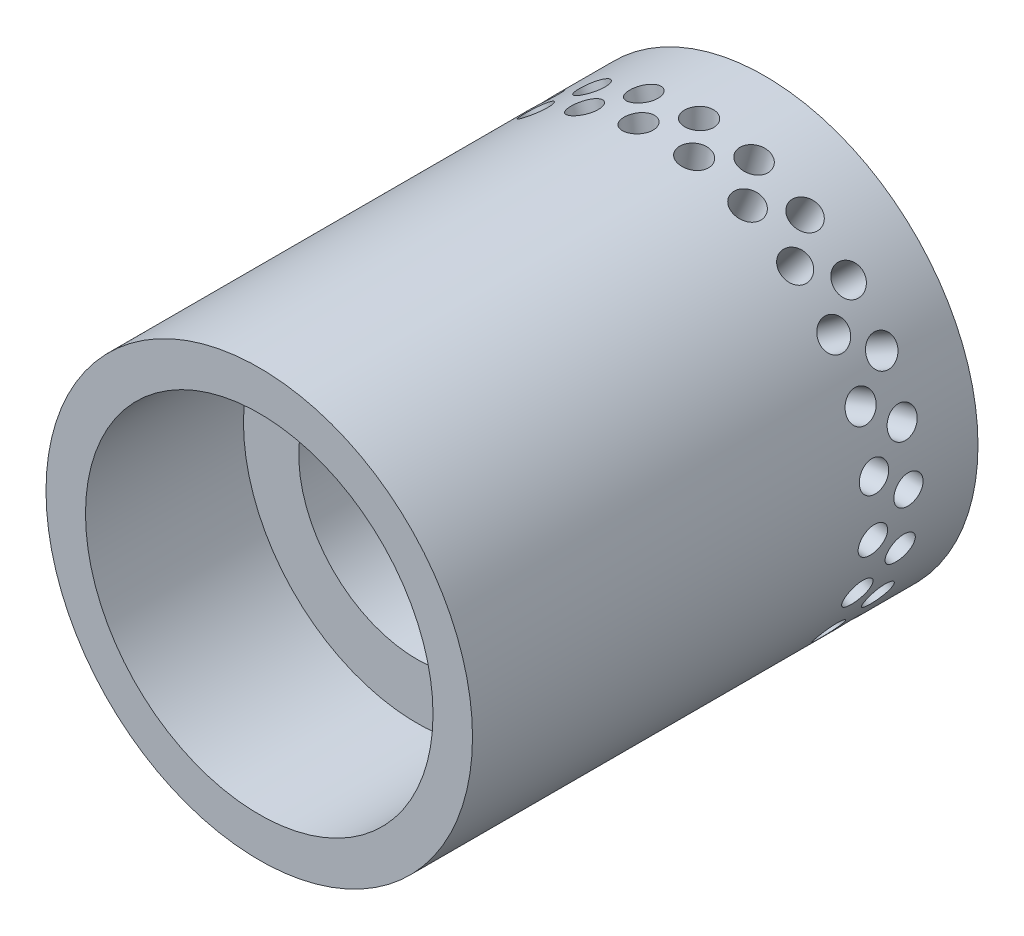
SolidWorks part; units mm, degrees
ref_plane "Front Plane" through (0, 0, 0) normal (0, 0, 1) x (1, 0, 0)
ref_plane "Top Plane" through (0, 0, 0) normal (0, 1, 0) x (1, 0, 0)
ref_plane "Right Plane" through (0, 0, 0) normal (1, 0, 0) x (0, 0, -1)
sketch "Sketch2" plane through (0, 0, 0) normal (0, 0, 1) x (1, 0, 0)
  circle A0 centre (0, 0) radius 13.5
  dimension "D1" = 27
extrude "Boss-Extrude1" add sketch "Sketch2" against normal blind 32
ref_plane "Plane1" through (0, 0, 0) normal (0, 0, 1) x (1, 0, 0)
sketch "Sketch4" plane through (0, 0, 0) normal (0, 0, 1) x (1, 0, 0)
  circle A0 centre (0, 0) radius 11
  dimension "D1" = 22
extrude "Cut-Extrude1" cut sketch "Sketch4" against normal blind 10
sketch "Sketch5" plane through (0, 0, 0) normal (0, 0, 1) x (1, 0, 0)
  circle A0 centre (0, 0) radius 7.5
  dimension "D1" = 15
extrude "Cut-Extrude2" cut sketch "Sketch5" against normal blind 30
hole_wizard "Ø1.85 (1.85) Diameter Hole1" positions "3DSketch1" profile "Sketch6" hole size "Ø1.85" standard "ANSI Metric" end condition through all
sketch3d "3DSketch1"
  point P0 (12.9749, -3.7284, -27.6)
  dimension "D1" = 4.4
sketch "Sketch6" plane through (12.9749, -3.7284, -27.6) normal (0, 0, 1) x (0.2762, 0.9611, 0)
  line L0 (0, 0) -> (0, 32.0274)
  line L1 (0, 32.0274) -> (0.925, 32.0274)
  line L2 (0.925, 32.0274) -> (0.925, 0)
  line L5 (0.925, 0) -> (0, 0)
  line L11 (0, -6.35) -> (0, 107.95) construction
  dimension "Thru Hole Dia." = 1.85
  dimension "Thru Hole Depth" = 32.0274
pattern_circular "CirPattern1" count 24 over 360 about axis through (0, 0, -32) along (0, 0, 1) of "Ø1.85 (1.85) Diameter Hole1"
hole_wizard "Ø1.85 (1.85) Diameter Hole2" positions "3DSketch2" profile "Sketch7" hole size "Ø1.85" standard "ANSI Metric" end condition through all
sketch3d "3DSketch2"
  point P0 (12.5743, 4.913, -25.5)
  dimension "D1" = 6.5
sketch "Sketch7" plane through (12.5743, 4.913, -25.5) normal (0, 0, 1) x (-0.3639, 0.9314, 0)
  line L0 (0, 0) -> (0, 28.4085)
  line L1 (0, 28.4085) -> (0.925, 28.4085)
  line L2 (0.925, 28.4085) -> (0.925, 0)
  line L5 (0.925, 0) -> (0, 0)
  line L11 (0, -6.35) -> (0, 107.95) construction
  dimension "Thru Hole Dia." = 1.85
  dimension "Thru Hole Depth" = 28.4085
pattern_circular "CirPattern2" count 24 over 360 about axis through (0, 0, -32) along (0, 0, 1) of "Ø1.85 (1.85) Diameter Hole2"
